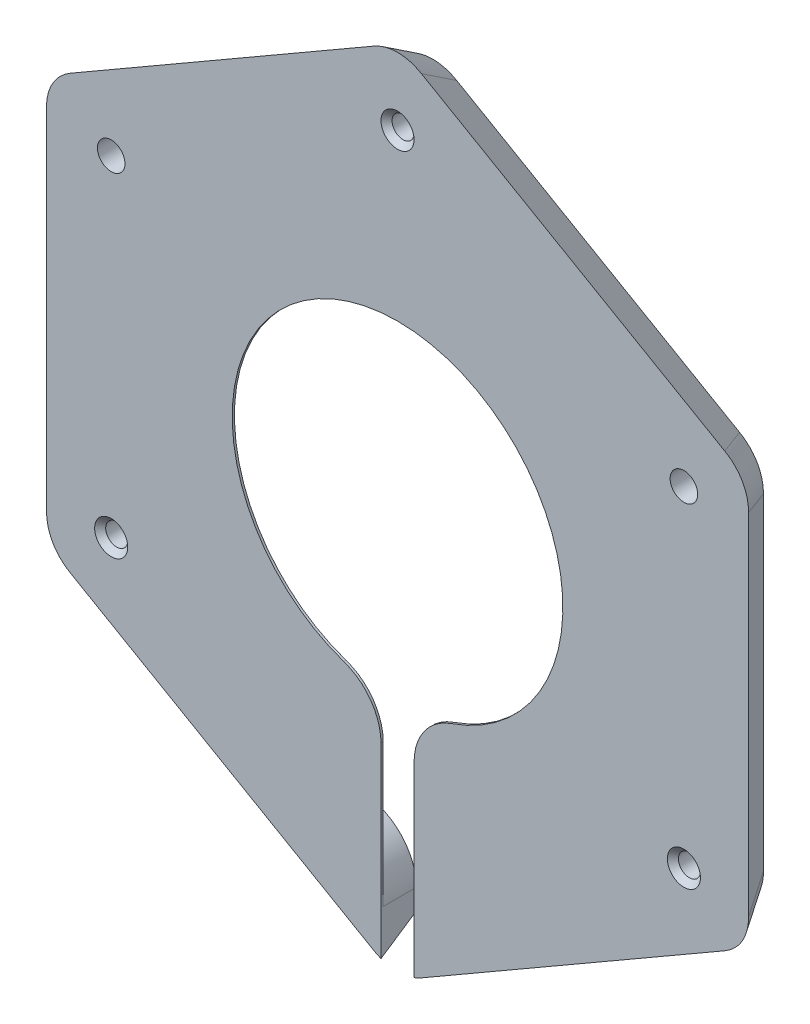
SolidWorks part; units mm, degrees
ref_plane "Front Plane" through (0, 0, 0) normal (0, 0, 1) x (1, 0, 0)
ref_plane "Top Plane" through (0, 0, 0) normal (0, 1, 0) x (1, 0, 0)
ref_plane "Right Plane" through (0, 0, 0) normal (1, 0, 0) x (0, 0, -1)
sketch "Sketch1" plane through (0, 0, 0) normal (0, 0, 1) x (1, 0, 0)
  line L1 (0, 69.282) -> (-60, 34.641)
  line L2 (-60, 34.641) -> (-60, -34.641)
  line L3 (-60, -34.641) -> (0, -69.282)
  line L4 (0, -69.282) -> (60, -34.641)
  line L5 (60, -34.641) -> (60, 34.641)
  line L6 (60, 34.641) -> (0, 69.282)
  circle A0 centre (0, 0) radius 60 construction
  dimension "D1" = 120
extrude "Boss-Extrude1" add sketch "Sketch1" along normal blind 6.4 draft 30 draft outward yes
fillet "Fillet1" radius 10 6 edges at (61.8475, -35.7077, 3.2) (0, -71.4154, 3.2) (-61.8475, -35.7077, 3.2) (-61.8475, 35.7077, 3.2) (0, 71.4154, 3.2) (61.8475, 35.7077, 3.2)
sketch "Sketch13" plane through (0, 0, 6.4) normal (0, 0, 1) x (1, 0, 0)
  circle A0 centre (0, 60) radius 2
  dimension "D1" = 4
  dimension "D2" = 60
extrude "Cut-Extrude3" cut sketch "Sketch13" against normal blind 5
sketch "Sketch14" plane through (0, 0, 0) normal (0, 0, -1) x (-1, 0, 0)
  circle A0 centre (0, 60) radius 1.5
  dimension "D1" = 3
  dimension "D2" = 60
extrude "Cut-Extrude4" cut sketch "Sketch14" against normal through all
sketch "Sketch15" plane through (0, 0, 0) normal (0, 0, -1) x (-1, 0, 0)
  circle A0 centre (0, 0) radius 55
  dimension "D1" = 110
extrude "Cut-Extrude5" cut sketch "Sketch15" against normal blind 6
pattern_circular "CirPattern9" count 3 over 360 about axis through (0, 0, 0) along (0, 0, -1) of "Cut-Extrude4", "Cut-Extrude3"
sketch "Sketch20" plane through (0, 0, 6) normal (0, 0, -1) x (-1, 0, 0)
  line L0 (-12.0829, 58) -> (-4, 44)
  line L1 (-4, 44) -> (4, 44)
  line L2 (4, 44) -> (12.0829, 58)
  line L3 (12.0829, 58) -> (-12.0829, 58)
  point P2 (0, 58)
  point P5 (0, 44)
  dimension "D1" = 60
  dimension "D2" = 14
  dimension "D3" = 44
  dimension "D4" = 8
extrude "Boss-Extrude4" add sketch "Sketch20" along normal blind 6
sketch "Sketch21" plane through (0, 44, 0) normal (0, -1, 0) x (-1, 0, 0)
  line L0 (-4, -6) -> (4, -6) construction
  line L1 (-2, -4) -> (2, -4)
  line L2 (-2, -4) -> (-2, -6)
  line L3 (-2, -6) -> (2, -6)
  line L4 (2, -4) -> (2, -6)
  line L5 (-4, 0) -> (4, 0) construction
  point P6 (0, -4)
  point P9 (0, 0)
  dimension "D1" = 2
  dimension "D2" = 4
revolve "Cut-Revolve1" cut sketch "Sketch21" angle 360 about axis through (4, 44, 0) along (-1, 0, 0)
fillet "Fillet8" radius 1 1 edges at (0, 48, 0)
pattern_circular "CirPattern11" count 3 over 120 about axis through (0, 0, 0) along (0, 0, -1) of "Boss-Extrude4", "Cut-Revolve1", "Fillet8"
sketch "Sketch16" plane through (0, 0, 0) normal (0, 0, -1) x (-1, 0, 0)
  circle A0 centre (0, -60) radius 2.5
  dimension "D1" = 5
  dimension "D2" = 60
extrude "Cut-Extrude6" cut sketch "Sketch16" against normal through all
pattern_circular "CirPattern10" count 3 over 360 about axis through (0, 0, 6) along (0, 0, -1) of "Cut-Extrude6"
sketch "Sketch22" plane through (0, 0, 6.4) normal (0, 0, 1) x (1, 0, 0)
  line L2 (-3, -37.8286) -> (-3, -80)
  line L3 (-3, -80) -> (3, -80)
  line L4 (3, -37.8286) -> (3, -80)
  arc A0 (9.75, -28.3714) -> (-9.75, -28.3714) centre (0, 0) ccw
  arc A1 (-3, -37.8286) -> (-9.75, -28.3714) centre (-13, -37.8286) ccw
  arc A2 (3, -37.8286) -> (9.75, -28.3714) centre (13, -37.8286) cw
  dimension "D1" = 60
  dimension "D5" = 10
  dimension "D2" = 6
  dimension "D3" = 80
  dimension "D4" = 3
extrude "Cut-Extrude7" cut sketch "Sketch22" against normal through all
fillet "Fillet9" radius 10 2 edges at (-3, -54.9181, 3) (3, -54.9181, 3)
fillet "Fillet10" radius 3 12 edges at (-9.8387, 54.1129, 3) (-4, 44, 3) (4, 44, 3) (9.8387, 54.1129, 3) (41.9438, 35.577, 3) (36.1051, 25.4641, 3) (40.1051, 18.5359, 3) (51.7824, 18.5359, 3) (51.7824, -18.5359, 3) (40.1051, -18.5359, 3) (36.1051, -25.4641, 3) (41.9438, -35.577, 3)
chamfer "Chamfer2" distance 1 angle 45 3 edges at (-52.9615, -28.2679, 6.4) (50.9615, -31.7321, 6.4) (2, 60, 6.4)
